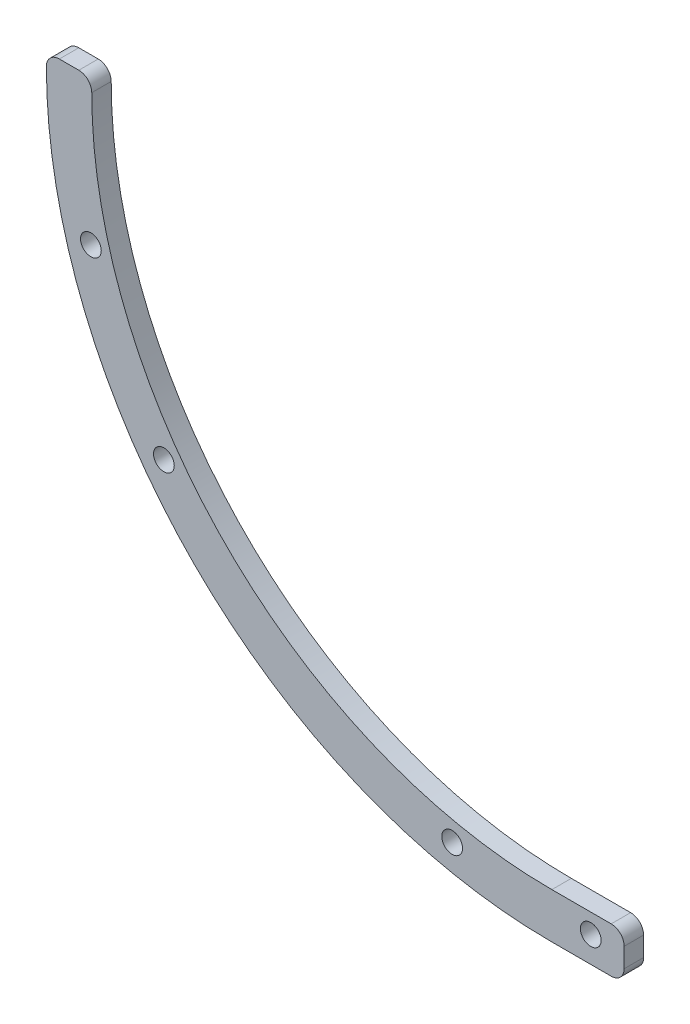
SolidWorks part; units mm, degrees
material "A-玻璃纤维"
ref_plane "前视基准面" through (0, 0, 0) normal (0, 0, 1) x (1, 0, 0)
ref_plane "上视基准面" through (0, 0, 0) normal (0, 1, 0) x (1, 0, 0)
ref_plane "右视基准面" through (0, 0, 0) normal (1, 0, 0) x (0, 0, -1)
sketch "草图1" plane through (0, 0, 0) normal (0, 0, 1) x (1, 0, 0)
  line L0 (-139.1546, 76.5) -> (-139.1546, -33.6254) construction
  line L1 (-91.6495, 50) -> (0, 50) construction
  line L2 (-90.2793, 53) -> (-5.3283, 53) construction
  line L4 (-99.1546, 26.5) -> (0, 26.5) construction
  line L6 (-99.1546, 26.5) -> (-88, 26.5) construction
  line L7 (0, 26.5) -> (0, 0) construction
  line L8 (-88, 26.5) -> (-88, -20.8435) construction
  arc A0 (-139.1546, 66.5) -> (-99.1546, 26.5) centre (-99.1546, 66.5) ccw
  dimension "D1" = 3
  dimension "D4" = 80
  dimension "D3" = 23.5
  dimension "D7" = 10
  dimension "D8" = 88
  dimension "D9" = 11.1546
sketch "草图2" plane through (0, 0, 0) normal (0, 0, 1) x (1, 0, 0)
  line L0 (0, 0) -> (-88, 0) construction
  line L1 (-88, 26.5) -> (-88, -20.8435) construction
  line L2 (0, 3) -> (-88, 3) construction
  line L3 (-99.1546, 26.5) -> (0, 26.5) construction
  line L4 (-139.1546, 76.5) -> (-139.1546, -33.6254) construction
  line L5 (-99.1546, 26.5) -> (-88, 26.5) construction
  line L6 (-139.1546, 76.5) -> (-139.1546, 66.5) construction
  line L7 (-88, 3) -> (-88, 26.5) construction
  line L8 (-161.1546, 76.5) -> (-161.1546, 66.5) construction
  line L9 (-99.1546, 4.5) -> (-88, 4.5) construction
  line L10 (-117.1546, 76.5) -> (-117.1546, 66.5) construction
  line L11 (-99.1546, 48.5) -> (-88, 48.5) construction
  line L13 (-162.1546, 76.5) -> (-162.1546, 66.5)
  line L14 (-99.1546, 3.5) -> (-88, 3.5)
  line L15 (-164.6546, 76.5) -> (-164.6546, 66.5) construction
  line L16 (-99.1546, 1) -> (-88, 1) construction
  line L17 (-169.1546, 76.5) -> (-169.1546, 66.5) construction
  line L18 (-99.1546, -3.5) -> (-88, -3.5) construction
  line L19 (-177.1546, 76.5) -> (-177.1546, 66.5)
  line L20 (-99.1546, -11.5) -> (-88, -11.5)
  line L21 (-177.1546, 76.5) -> (-162.1546, 76.5)
  line L22 (-88, 3.5) -> (-88, -11.5)
  line L23 (-99.1546, 66.5) -> (-99.1546, 1) construction
  line L24 (-99.1546, 66.5) -> (-106.9101, 1.4608) construction
  line L25 (-164.6546, 75.2931) -> (-164.6546, 78.7931) construction
  line L26 (-99.1546, 66.5) -> (-99.1546, 1) construction
  line L27 (-99.1546, 66.5) -> (-106.9101, 1.4608) construction
  arc A0 (-139.1546, 66.5) -> (-99.1546, 26.5) centre (-99.1546, 66.5) ccw construction
  arc A1 (-139.1546, 66.5) -> (-99.1546, 26.5) centre (-99.1546, 66.5) ccw construction
  arc A2 (-161.1546, 66.5) -> (-99.1546, 4.5) centre (-99.1546, 66.5) ccw construction
  arc A3 (-117.1546, 66.5) -> (-99.1546, 48.5) centre (-99.1546, 66.5) ccw construction
  arc A4 (-162.1546, 66.5) -> (-99.1546, 3.5) centre (-99.1546, 66.5) ccw
  arc A5 (-164.6546, 66.5) -> (-99.1546, 1) centre (-99.1546, 66.5) ccw construction
  arc A6 (-169.1546, 66.5) -> (-99.1546, -3.5) centre (-99.1546, 66.5) ccw construction
  arc A7 (-177.1546, 66.5) -> (-99.1546, -11.5) centre (-99.1546, 66.5) ccw
  circle A8 centre (-91.7546, 1) radius 3.5 construction
  circle A9 centre (-99.1546, 1) radius 3.5 construction
  circle A10 centre (-106.9101, 1.4608) radius 3.5 construction
  circle A11 centre (-114.5564, 2.8366) radius 3.5 construction
  circle A12 centre (-121.9861, 5.108) radius 3.5 construction
  circle A13 centre (-129.0945, 8.2432) radius 3.5 construction
  circle A14 centre (-135.7817, 12.198) radius 3.5 construction
  circle A15 centre (-141.9536, 16.9168) radius 3.5 construction
  circle A16 centre (-147.5234, 22.3332) radius 3.5 construction
  circle A17 centre (-152.4127, 28.3709) radius 3.5 construction
  circle A18 centre (-156.5527, 34.9451) radius 3.5 construction
  circle A19 centre (-159.8851, 41.9633) radius 3.5 construction
  circle A20 centre (-162.3632, 49.3266) radius 3.5 construction
  circle A21 centre (-163.9519, 56.9316) radius 3.5 construction
  circle A22 centre (-164.6291, 64.6711) radius 3.5 construction
  circle A23 centre (-164.6546, 72.3711) radius 3.5 construction
  arc A24 (-139.1546, 66.5) -> (-99.1546, 26.5) centre (-99.1546, 66.5) ccw construction
  circle A26 centre (-91.7546, 1) radius 1.6
  circle A27 centre (-99.1546, 1) radius 1.6
  circle A28 centre (-106.9101, 1.4608) radius 1.6
  circle A29 centre (-114.5564, 2.8366) radius 1.6
  circle A30 centre (-121.9861, 5.108) radius 1.6
  circle A31 centre (-129.0945, 8.2432) radius 1.6
  circle A32 centre (-135.7817, 12.198) radius 1.6
  circle A33 centre (-141.9536, 16.9168) radius 1.6
  circle A34 centre (-147.5234, 22.3332) radius 1.6
  circle A35 centre (-152.4127, 28.3709) radius 1.6
  circle A36 centre (-156.5527, 34.9451) radius 1.6
  circle A37 centre (-159.8851, 41.9633) radius 1.6
  circle A38 centre (-162.3632, 49.3266) radius 1.6
  circle A39 centre (-163.9519, 56.9316) radius 1.6
  circle A40 centre (-164.6291, 64.6711) radius 1.6
  circle A41 centre (-164.6546, 72.3711) radius 1.6
  dimension "D8" = 7
  dimension "D9" = 7
  dimension "D10" = 7.4
  dimension "D13" = 7
  dimension "D16" = 3.2
  dimension "D17" = 3.2
  dimension "D20" = 3.2
  dimension "D1" = 3
  dimension "D2" = 22
  dimension "D4" = 1
  dimension "D12" = 6.8
  dimension "D14" = 7.7691
  dimension "D15" = 7.7
  dimension "D19" = 6.8
  dimension "D3" = 22
  dimension "D5" = 3.5
  dimension "D6" = 7
  dimension "D7" = 8
  dimension "D11" = 14
  dimension "D18" = 14
extrude "凸台-拉伸1" add sketch "草图2" along normal blind 3
sketch "草图3" plane through (0, 0, 3) normal (0, 0, 1) x (1, 0, 0)
  line L0 (0, 0) -> (-88, 0) construction
  line L1 (-88, 26.5) -> (-88, -20.8435) construction
  line L2 (-88, 0) -> (-88, -3) construction
  line L3 (-88, -3) -> (-79.8645, -3) construction
  line L4 (-177.1546, 76.5) -> (-177.1546, 66.5) construction
  line L5 (-99.1546, -11.5) -> (-88, -11.5) construction
  line L6 (-177.1546, 76.5) -> (-177.1546, 66.5) construction
  line L7 (-99.1546, -11.5) -> (-88, -11.5) construction
  line L8 (-173.1546, 76.5) -> (-173.1546, 66.5) construction
  line L9 (-99.1546, -7.5) -> (-88, -7.5) construction
  arc A0 (-177.1546, 66.5) -> (-99.1546, -11.5) centre (-99.1546, 66.5) ccw construction
  arc A1 (-177.1546, 66.5) -> (-99.1546, -11.5) centre (-99.1546, 66.5) ccw construction
  arc A2 (-173.1546, 66.5) -> (-99.1546, -7.5) centre (-99.1546, 66.5) ccw construction
  dimension "D2" = 4
  dimension "D1" = 3
sketch "草图4" plane through (0, 0, 3) normal (0, 0, 1) x (1, 0, 0)
  line L0 (-181.7432, 78.5) -> (-173.2222, 78.5) construction
  line L1 (-162.1546, 76.5) -> (-177.1546, 76.5) construction
  line L2 (-187.8077, 70) -> (-181.0523, 70) construction
  line L3 (-177.1546, 68.5) -> (-170.6546, 68.5)
  line L4 (-177.1546, 76.5) -> (-177.1546, 66.5) construction
  line L5 (-170.6546, 68.5) -> (-170.6546, 76.5)
  line L6 (-170.6546, 76.5) -> (-177.1546, 76.5)
  line L7 (-177.1546, 76.5) -> (-177.1546, 68.5)
  dimension "D1" = 2
  dimension "D2" = 8.5
  dimension "D3" = 1.5
  dimension "D4" = 6.5
extrude "切除-拉伸1" cut sketch "草图4" against normal blind 3
sketch "草图6" plane through (0, 0, 3) normal (0, 0, 1) x (1, 0, 0)
  line L0 (-99.1546, -7.5) -> (-88, -7.5) construction
  line L1 (-99.1546, -11.5) -> (-99.1546, 66.5) construction
  line L2 (-99.1546, 66.5) -> (-114.5401, -5.8829) construction
  line L3 (-159.0218, 23.0039) -> (-99.1546, 66.5) construction
  line L4 (-99.1546, 66.5) -> (-170.288, 46.1028) construction
  line L5 (-99.1546, 66.5) -> (-194.6638, 66.5) construction
  circle A0 centre (-170.288, 46.1028) radius 1.6
  arc A1 (-173.1546, 66.5) -> (-99.1546, -7.5) centre (-99.1546, 66.5) ccw construction
  circle A2 centre (-159.0218, 23.0039) radius 1.6
  circle A3 centre (-114.5401, -5.8829) radius 1.6
  circle A4 centre (-93.1546, -7.5) radius 1.6
  dimension "D1" = 3.2
  dimension "D2" = 3.2
  dimension "D3" = 3.2
  dimension "D4" = 3.2
  dimension "D8" = 6
  dimension "D5" = 16
  dimension "D6" = 20
  dimension "D7" = 12
extrude "切除-拉伸2" cut sketch "草图6" against normal blind 10
sketch "草图8" plane through (0, 0, 3) normal (0, 0, 1) x (1, 0, 0)
  line L0 (-88, 3.5) -> (-99.1546, 3.5) construction
  line L1 (-162.1546, 66.5) -> (-162.1546, 76.5) construction
  line L2 (-88, 3.5) -> (-99.1546, 3.5)
  line L3 (-162.1546, 66.5) -> (-162.1546, 76.5)
  line L4 (-88, -4.5) -> (-99.1546, -4.5)
  line L5 (-170.1546, 66.5) -> (-170.1546, 68.5)
  line L6 (-88, 3.5) -> (-88, -4.5)
  line L7 (-170.6546, 68.5) -> (-170.1546, 68.5)
  line L8 (-170.1546, 66.5) -> (-170.1546, 76.5) construction
  line L9 (-170.6546, 68.5) -> (-170.6546, 76.5)
  line L10 (-170.6546, 76.5) -> (-162.1546, 76.5)
  arc A0 (-162.1546, 66.5) -> (-99.1546, 3.5) centre (-99.1546, 66.5) ccw construction
  arc A1 (-162.1546, 66.5) -> (-99.1546, 3.5) centre (-99.1546, 66.5) ccw
  arc A2 (-170.1546, 66.5) -> (-99.1546, -4.5) centre (-99.1546, 66.5) ccw
  dimension "D1" = 8
extrude "切除-拉伸3" cut sketch "草图8" against normal blind 10
fillet "圆角1" radius 2 4 edges at (-177.1546, 68.5, 1.5) (-88, -11.5, 1.5) (-88, -4.5, 1.5) (-170.1546, 68.5, 1.5)
